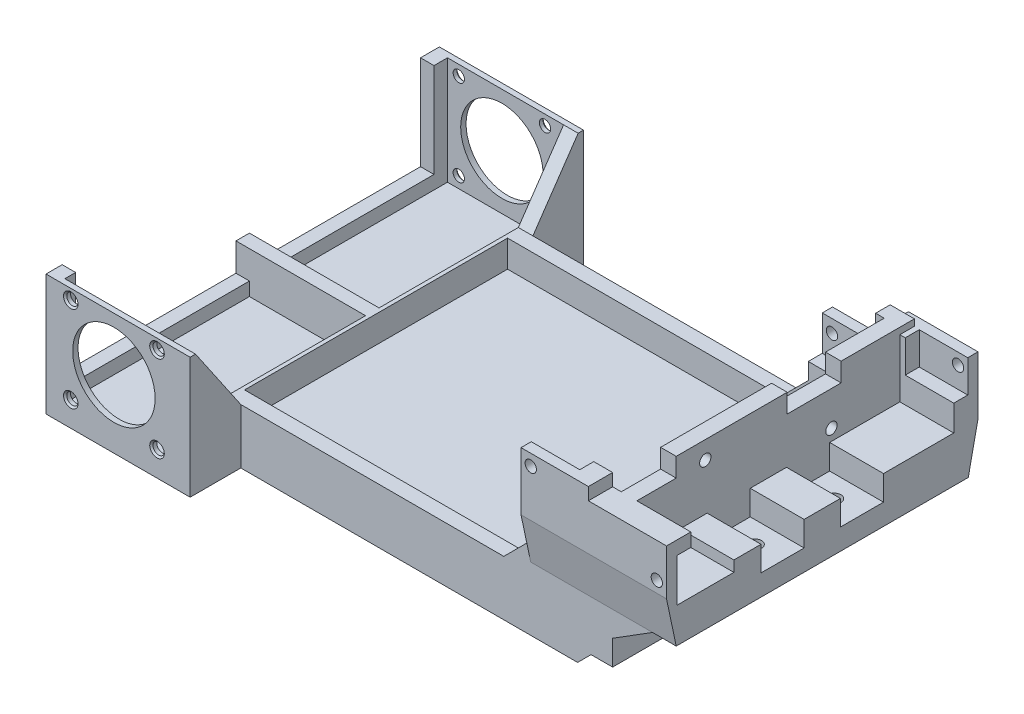
SolidWorks part; units mm, degrees
ref_plane "Front Plane" through (0, 0, 0) normal (0, 0, 1) x (1, 0, 0)
ref_plane "Top Plane" through (0, 0, 0) normal (0, 1, 0) x (1, 0, 0)
ref_plane "Right Plane" through (0, 0, 0) normal (1, 0, 0) x (0, 0, -1)
sketch "Sketch1" plane through (0, 0, 0) normal (0, 1, 0) x (1, 0, 0)
  line L0 (-12.1, 32.5) -> (-12.1, 35.5)
  line L1 (83.8983, -32.4) -> (56.8983, -32.4)
  line L2 (83.8983, -32.4) -> (83.8983, -47)
  line L3 (83.8983, -47) -> (56.8983, -47)
  line L4 (56.8983, -32.4) -> (56.8983, -47)
  line L5 (83.3, 13.5) -> (97.9, 13.5)
  line L6 (83.3, 13.5) -> (83.3, -13.5)
  line L7 (83.3, -13.5) -> (97.9, -13.5)
  line L8 (97.9, 13.5) -> (97.9, -13.5)
  line L9 (56.8983, 32.4) -> (83.8983, 32.4)
  line L10 (56.8983, 32.4) -> (56.8983, 47)
  line L11 (56.8983, 47) -> (83.8983, 47)
  line L12 (83.8983, 32.4) -> (83.8983, 47)
  line L13 (14.3, -24.25) -> (80.3, -24.25)
  line L14 (14.3, -24.25) -> (14.3, 24.25)
  line L15 (14.3, 24.25) -> (80.3, 24.25)
  line L16 (80.3, -24.25) -> (80.3, 24.25)
  line L17 (-12.1, 2.5) -> (10.1, 2.5)
  line L18 (-12.1, 2.5) -> (-12.1, 10.5)
  line L19 (-12.1, 35.5) -> (10.1, 35.5)
  line L20 (10.1, 2.5) -> (10.1, 10.5)
  line L21 (10.1, -35.5) -> (-10.1, -35.5)
  line L22 (10.1, -35.5) -> (10.1, -32.5)
  line L23 (10.1, -2.5) -> (-10.1, -2.5)
  line L24 (-10.1, -35.5) -> (-10.1, -32.5)
  line L25 (-16.1, -32.5) -> (-10.1, -32.5)
  line L26 (-16.1, -32.5) -> (-16.1, -10.5)
  line L27 (-16.1, -10.5) -> (-10.1, -10.5)
  line L28 (11.3, -32.5) -> (11.3, -10.5)
  line L29 (-16.1, 10.5) -> (-12.1, 10.5)
  line L30 (-16.1, 10.5) -> (-16.1, 32.5)
  line L31 (-16.1, 32.5) -> (-12.1, 32.5)
  line L32 (11.3, 10.5) -> (11.3, 32.5)
  line L33 (10.1, 10.5) -> (11.3, 10.5)
  line L34 (10.1, 32.5) -> (10.1, 35.5)
  line L35 (10.1, 32.5) -> (11.3, 32.5)
  line L36 (10.1, -10.5) -> (11.3, -10.5)
  line L37 (10.1, -10.5) -> (10.1, -2.5)
  line L38 (-10.1, -10.5) -> (-10.1, -2.5)
  line L39 (10.1, -32.5) -> (11.3, -32.5)
  arc A0 (86.0992, 6.7139) -> (86.0992, -6.7139) centre (89.8, 0) ccw
  arc A1 (87.0805, -8.0067) -> (92.5195, -8.0067) centre (89.8, -7.366) ccw
  arc A2 (92.5195, 8.0067) -> (87.0805, 8.0067) centre (89.8, 7.366) ccw
  arc A3 (93.5008, -6.7139) -> (93.5008, 6.7139) centre (89.8, 0) ccw
  arc A4 (92.5195, -8.0067) -> (93.5008, -6.7139) centre (94.4662, -8.4654) cw
  arc A5 (86.0992, 6.7139) -> (87.0805, 8.0067) centre (85.1338, 8.4654) ccw
  arc A6 (87.0805, -8.0067) -> (86.0992, -6.7139) centre (85.1338, -8.4654) ccw
  arc A7 (93.5008, 6.7139) -> (92.5195, 8.0067) centre (94.4662, 8.4654) cw
  point P33 (92.585, -7.1425)
  dimension "D1" = 2
  dimension "D2" = 2
  dimension "D3" = 2
  dimension "D36" = 7.6663
  dimension "D37" = 7.366
  dimension "D39" = 2.794
  dimension "D4" = 22.2
  dimension "D5" = 3
  dimension "D6" = 22
  dimension "D7" = 4
  dimension "D8" = 1.2
  dimension "D9" = 3
  dimension "D10" = 66
  dimension "D11" = 48.5
  dimension "D12" = 20.2
  dimension "D13" = 6
  dimension "D14" = 1.2
  dimension "D15" = 3
  dimension "D16" = 22
  dimension "D17" = 8
  dimension "D18" = 3
  dimension "D19" = 11.5
  dimension "D20" = 11.5
  dimension "D21" = 27
  dimension "D22" = 14.6
  dimension "D23" = 27
  dimension "D24" = 14.6
  dimension "D25" = 45.5983
  dimension "D26" = 45.5983
  dimension "D27" = 8
  dimension "D28" = 5
  dimension "D29" = 8.15
  dimension "D30" = 3
  dimension "D31" = 10.75
  dimension "D32" = 9.5
  dimension "D33" = 24.25
  dimension "D34" = 27
  dimension "D35" = 14.6
  dimension "D38" = 7.366
  dimension "D40" = 14.3
  dimension "D41" = 2.5
sketch "Sketch5" plane through (0, 0, 0) normal (0, 1, 0) x (1, 0, 0)
  line L0 (83.15, 27.1) -> (11.45, 27.1)
  line L1 (80.3, 24.25) -> (14.3, 24.25) construction
  line L2 (80.3, 24.25) -> (80.3, -24.25) construction
  line L3 (80.3, -24.25) -> (14.3, -24.25) construction
  line L4 (14.3, 24.25) -> (14.3, -24.25) construction
  line L5 (11.45, 27.1) -> (11.45, -27.1)
  line L6 (83.15, -27.1) -> (11.45, -27.1)
  line L7 (83.15, 27.1) -> (83.15, 3.8718)
  line L8 (83.15, -3.8718) -> (83.15, -27.1)
  line L9 (14.15, 24.4) -> (14.15, -24.4)
  line L10 (83.15, 27.1) -> (83.15, -27.1) construction
  line L11 (80.45, -24.4) -> (14.15, -24.4)
  line L12 (80.45, 24.4) -> (80.45, -24.4)
  line L13 (80.45, 24.4) -> (14.15, 24.4)
  arc A0 (83.15, 3.8718) -> (83.15, -3.8718) centre (89.8, 0) ccw
  dimension "D2" = 15.39
  dimension "D1" = 2.85
  dimension "D3" = 0.15
extrude "Boss-Extrude2" add sketch "Sketch5" along normal blind 5
sketch "Sketch6" plane through (0, 0, 0) normal (0, -1, 0) x (1, 0, 0)
  line L0 (83.15, -3.8718) -> (83.15, -27.1)
  line L1 (11.45, 27.1) -> (83.15, 27.1)
  line L2 (11.45, 27.1) -> (11.45, -27.1)
  line L3 (11.45, -27.1) -> (83.15, -27.1)
  line L4 (83.15, 27.1) -> (83.15, 3.8718)
  arc A0 (83.15, 3.8718) -> (83.15, -3.8718) centre (89.8, 0) ccw
  dimension "D1" = 15.39
extrude "Boss-Extrude4" add sketch "Sketch6" along normal blind 2.7
sketch "Sketch7" plane through (0, 5, 0) normal (0, 1, 0) x (1, 0, 0)
  line L1 (83.15, -27.1) -> (75.15, -27.1)
  line L2 (11.45, -27.1) -> (83.15, -27.1) construction
  line L3 (75.15, -27.1) -> (75.15, -24.4)
  line L4 (14.15, -24.4) -> (80.45, -24.4) construction
  line L5 (75.15, -24.4) -> (80.45, -24.4)
  line L6 (80.45, -24.4) -> (80.45, 24.4)
  line L7 (80.45, 24.4) -> (75.15, 24.4)
  line L8 (80.45, 24.4) -> (14.15, 24.4) construction
  line L9 (75.15, 24.4) -> (75.15, 27.1)
  line L10 (83.15, 27.1) -> (11.45, 27.1) construction
  line L11 (75.15, 27.1) -> (83.15, 27.1)
  line L14 (83.15, 27.1) -> (83.15, 3.8718)
  line L15 (83.15, -3.8718) -> (83.15, -27.1)
  arc A0 (83.15, 3.8718) -> (83.15, -3.8718) centre (89.8, 0) ccw
  dimension "D1" = 15.39
  dimension "D2" = 8
  dimension "D3" = 8
extrude "Boss-Extrude5" add sketch "Sketch7" along normal blind 1.575
sketch "Sketch8" plane through (0, 6.575, 0) normal (0, 1, 0) x (1, 0, 0)
  line L0 (75.15, -27.1) -> (83.15, -27.1) construction
  line L1 (80.45, -27.1) -> (97.95, -27.1)
  line L2 (80.45, -27.1) -> (80.45, 27.1)
  line L3 (80.45, 27.1) -> (97.95, 27.1)
  line L4 (97.95, -27.1) -> (97.95, 27.1)
  line L5 (80.45, -27.1) -> (83.15, -27.1) construction
  dimension "D1" = 54.2
  dimension "D2" = 17.5
  dimension "D3" = 2.7
extrude "Boss-Extrude6" add sketch "Sketch8" along normal blind 8.5
sketch "Sketch9" plane through (0, 0, 27.1) normal (0, 0, 1) x (1, 0, 0)
  line L0 (80.45, 15.075) -> (75.15, 6.575)
  line L1 (75.15, 6.575) -> (80.45, 6.575)
  line L2 (80.45, 6.575) -> (80.45, 15.075)
extrude "Boss-Extrude7" add sketch "Sketch9" against normal through all
sketch "Sketch10" plane through (0, 0, 0) normal (0, 1, 0) x (1, 0, 0)
  line L0 (80.45, 27.1) -> (80.45, -27.1) construction
  line L1 (14.15, 24.4) -> (80.45, 24.4)
  line L2 (14.15, 24.4) -> (14.15, -24.4)
  line L3 (14.15, -24.4) -> (80.45, -24.4)
  line L4 (80.45, 24.4) -> (80.45, -24.4)
  line L5 (14.15, -24.4) -> (80.45, -24.4) construction
extrude "Cut-Extrude1" cut sketch "Sketch10" along normal through all
sketch "Sketch11" plane through (0, 0, 27.1) normal (0, 0, 1) x (1, 0, 0)
  line L0 (90.55, 6.575) -> (83.15, 1.9375)
  line L1 (83.15, 6.575) -> (97.95, 6.575) construction
  line L2 (83.15, 6.575) -> (83.15, -2.7) construction
  line L3 (83.15, 1.9375) -> (83.15, 6.575)
  line L4 (83.15, 6.575) -> (90.55, 6.575)
extrude "Boss-Extrude8" add sketch "Sketch11" against normal blind 5
sketch "Sketch12" plane through (0, 0, -27.1) normal (0, 0, -1) x (-1, 0, 0)
  line L0 (-90.55, 6.575) -> (-83.15, 1.9375)
  line L1 (-97.95, 6.575) -> (-83.15, 6.575) construction
  line L2 (-83.15, 6.575) -> (-83.15, -2.7) construction
  line L3 (-83.15, 1.9375) -> (-83.15, 6.575)
  line L4 (-83.15, 6.575) -> (-90.55, 6.575)
extrude "Boss-Extrude9" add sketch "Sketch12" against normal blind 5
sketch "Sketch13" plane through (0, 15.075, 0) normal (0, 1, 0) x (1, 0, 0)
  line L1 (80.45, 27.1) -> (84.95, 27.1)
  line L2 (80.45, 27.1) -> (80.45, -27.1)
  line L3 (80.45, -27.1) -> (84.95, -27.1)
  line L4 (84.95, 27.1) -> (84.95, -27.1)
  dimension "D1" = 4.5
extrude "Boss-Extrude10" add sketch "Sketch13" along normal blind 12
sketch "Sketch15" plane through (0, 15.075, 0) normal (0, 1, 0) x (1, 0, 0)
  circle A0 centre (89.8, 7.366) radius 1.25
  circle A1 centre (89.8, -7.366) radius 1.25
  dimension "D1" = 2.5
  dimension "D2" = 2.5
extrude "Cut-Extrude3" cut sketch "Sketch15" against normal through all
sketch "Sketch16" plane through (0, 15.075, 0) normal (0, 1, 0) x (1, 0, 0)
  line L0 (89.8, -7.366) -> (89.8, 7.366) construction
  line L1 (89.8, -7.366) -> (84.95, -7.366) construction
  line L2 (84.95, -27.1) -> (84.95, 27.1) construction
  line L3 (84.95, -7.366) -> (84.95, -11.366) construction
  line L4 (89.8, 7.366) -> (84.95, 7.366) construction
  line L5 (84.95, -27.1) -> (84.95, 27.1) construction
  line L6 (84.95, 7.366) -> (84.95, 11.366) construction
  line L7 (97.95, -27.1) -> (97.95, 27.1) construction
  line L8 (84.95, 11.366) -> (97.95, 11.366)
  line L9 (84.95, 11.366) -> (84.95, 3.366)
  line L10 (84.95, -11.366) -> (97.95, -11.366)
  line L11 (97.95, 11.366) -> (97.95, 3.366)
  line L12 (84.95, -7.366) -> (84.95, -3.366) construction
  line L13 (84.95, -3.366) -> (97.95, -3.366)
  line L14 (84.95, 7.366) -> (84.95, 3.366) construction
  line L15 (84.95, 3.366) -> (97.95, 3.366)
  line L16 (84.95, -3.366) -> (84.95, -11.366)
  line L17 (97.95, -3.366) -> (97.95, -11.366)
  dimension "D1" = 4
  dimension "D2" = 4
  dimension "D3" = 4
  dimension "D4" = 4
extrude "Cut-Extrude4" cut sketch "Sketch16" against normal offset from surface (4.6 mm away) 3.9 up to face at (89.8, 6.575, -8.616)
sketch "Sketch17" plane through (0, 15.075, 0) normal (0, 1, 0) x (1, 0, 0)
  line L0 (84.95, -27.1) -> (97.95, -27.1) construction
  line L1 (97.95, 27.1) -> (94.95, 27.1)
  line L2 (97.95, 27.1) -> (97.95, -27.1)
  line L3 (97.95, -27.1) -> (94.95, -27.1)
  line L4 (94.95, 27.1) -> (94.95, -27.1)
  dimension "D1" = 3
extrude "Cut-Extrude5" cut sketch "Sketch17" against normal through all
sketch "Sketch18" plane through (80.45, 0, 0) normal (-1, 0, 0) x (0, 0, 1)
  line L0 (0, 27.075) -> (-13.5, 27.075) construction
  line L1 (-27.1, 27.075) -> (27.1, 27.075) construction
  line L3 (-13.5, 27.075) -> (-3.5, 27.075)
  line L4 (-13.5, 27.075) -> (-13.5, 23.575)
  line L5 (-13.5, 23.575) -> (-3.5, 23.575)
  line L6 (-3.5, 27.075) -> (-3.5, 23.575)
  dimension "D1" = 13.5
  dimension "D2" = 8.5
  dimension "D3" = 10
extrude "Cut-Extrude6" cut sketch "Sketch18" against normal through all
sketch "Sketch19" plane through (84.95, 0, 0) normal (1, 0, 0) x (0, 0, -1)
  line L0 (-27.1, 27.075) -> (27.1, 27.075) construction
  line L1 (0, 15.075) -> (0, 25.875) construction
  line L3 (-11.7, 20.475) -> (11.7, 20.475) construction
  line L4 (11.7, 20.475) -> (11.7, 17.175) construction
  line L5 (-11.7, 20.475) -> (-11.7, 23.775) construction
  line L7 (0, 27.075) -> (0, 25.875) construction
  line L8 (3.366, 15.075) -> (-3.366, 15.075) construction
  circle A0 centre (-11.7, 23.775) radius 1.05
  circle A1 centre (11.7, 17.175) radius 1.05
  point P6 (0, 0)
  point P11 (0, 20.475)
  point P15 (0, 20.475)
  dimension "D3" = 2.1
  dimension "D4" = 2.1
  dimension "D1" = 23.4
  dimension "D2" = 2.1
  dimension "D5" = 10.8
extrude "Cut-Extrude7" cut sketch "Sketch19" against normal through all
sketch "Sketch20" plane through (0, 27.075, 0) normal (0, 1, 0) x (1, 0, 0)
  line L2 (80.45, -24.4) -> (80.45, 24.4)
  line L4 (82.05, -24.4) -> (82.05, 24.4)
  line L5 (80.45, 27.1) -> (80.45, 24.4) construction
  line L6 (80.45, 24.4) -> (82.05, 24.4)
  line L7 (80.45, -27.1) -> (80.45, -24.4) construction
  line L8 (80.45, -24.4) -> (82.05, -24.4)
  dimension "D1" = 1.6
extrude "Cut-Extrude8" cut sketch "Sketch20" against normal blind 20
sketch "Sketch21" plane through (0, 0, 27.1) normal (0, 0, 1) x (1, 0, 0)
  line L0 (94.95, 15.075) -> (94.95, 17.175) construction
  line L1 (84.95, 15.075) -> (94.95, 15.075)
  line L2 (84.95, 15.075) -> (84.95, 20.075)
  line L3 (84.95, 20.075) -> (94.95, 20.075)
  line L4 (94.95, 15.075) -> (94.95, 20.075)
  line L5 (94.95, 17.175) -> (93.15, 17.175) construction
  line L6 (94.95, 6.575) -> (94.95, 15.075) construction
  circle A0 centre (93.15, 17.175) radius 1.05
  dimension "D4" = 2.1
  dimension "D1" = 5
  dimension "D2" = 2.1
  dimension "D3" = 1.8
extrude "Boss-Extrude11" add sketch "Sketch21" against normal blind 2.7 and the other way blind 1.8
sketch "Sketch23" plane through (0, 0, 27.1) normal (0, 0, 1) x (1, 0, 0)
  line L0 (67.95, 25.875) -> (67.95, 23.775) construction
  line L1 (94.95, 15.075) -> (67.95, 15.075)
  line L2 (94.95, 15.075) -> (94.95, 25.875)
  line L3 (94.95, 25.875) -> (67.95, 25.875)
  line L4 (67.95, 15.075) -> (67.95, 25.875)
  line L5 (67.95, 23.775) -> (69.75, 23.775) construction
  circle A0 centre (69.75, 23.775) radius 1.05
  circle A1 centre (93.15, 17.175) radius 1.05
  dimension "D5" = 2.1
  dimension "D6" = 2.1
  dimension "D1" = 10.8
  dimension "D2" = 27
  dimension "D3" = 2.1
  dimension "D4" = 1.8
extrude "Boss-Extrude13" add sketch "Sketch23" along normal blind 1.8 and the other way blind 2.7
sketch "Sketch22" plane through (82.05, 0, 0) normal (-1, 0, 0) x (0, 0, 1)
  line L1 (34.4916, 27.075) -> (17.1, 27.075)
  line L3 (27.9666, 23.575) -> (17.1, 23.575)
  line L4 (17.1, 27.075) -> (17.1, 23.575)
  line L5 (34.4916, 27.075) -> (34.4916, 23.575)
  line L6 (34.4916, 23.575) -> (27.9666, 23.575)
  line L7 (27.1, 27.075) -> (-3.5, 27.075) construction
  point P5 (34.4916, 25.575)
  dimension "D1" = 10
  dimension "D3" = 3.5
extrude "Cut-Extrude9" cut sketch "Sketch22" against normal through all and the other way up to surface (1.6 mm away) other way up to face at (80.45, 26.475, 25.75)
sketch "Sketch24" plane through (0, 0, 27.1) normal (0, 0, 1) x (1, 0, 0)
  line L1 (67.95, 15.075) -> (85.45, 15.075)
  line L2 (67.95, 15.075) -> (67.95, 5)
  line L3 (67.95, 5) -> (85.45, 5)
  line L4 (85.45, 15.075) -> (85.45, 5)
extrude "Boss-Extrude14" add sketch "Sketch24" against normal up to surface (2.7 mm away) up to face at (67.7577, 12.2904, 24.4)
sketch "Sketch25" plane through (0, 0, -27.1) normal (0, 0, -1) x (-1, 0, 0)
  line L0 (-94.95, 25.875) -> (-94.95, 23.775) construction
  line L1 (-94.95, 15.075) -> (-67.95, 15.075)
  line L2 (-94.95, 15.075) -> (-94.95, 25.875)
  line L3 (-94.95, 25.875) -> (-82.05, 25.875)
  line L5 (-94.95, 23.775) -> (-93.15, 23.775) construction
  line L6 (-67.95, 15.075) -> (-67.95, 17.175) construction
  line L7 (-67.95, 17.175) -> (-69.75, 17.175) construction
  line L9 (-67.95, 19.575) -> (-76.95, 19.575)
  line L10 (-76.95, 19.575) -> (-82.05, 25.875)
  line L11 (-67.95, 19.575) -> (-67.95, 15.075)
  circle A0 centre (-93.15, 23.775) radius 1.05
  circle A1 centre (-69.75, 17.175) radius 1.05
  dimension "D3" = 2.1
  dimension "D1" = 2.1
  dimension "D2" = 1.8
  dimension "D4" = 2.1
  dimension "D5" = 1.8
  dimension "D6" = 4.5
  dimension "D7" = 9
  dimension "D8" = 27
  dimension "D9" = 12.9
  dimension "D10" = 6.3
extrude "Boss-Extrude15" add sketch "Sketch25" along normal blind 1.8 and the other way blind 2.7
sketch "Sketch26" plane through (0, 0, -24.4) normal (0, 0, 1) x (1, 0, 0)
  line L0 (80.45, 15.075) -> (67.95, 15.075) construction
  line L1 (67.95, 19.575) -> (80.95, 19.575)
  line L2 (67.95, 19.575) -> (67.95, 15.075)
  line L3 (67.95, 15.075) -> (80.95, 15.075)
  line L4 (80.95, 19.575) -> (80.95, 15.075)
extrude "Cut-Extrude10" cut sketch "Sketch26" against normal blind 2.6
sketch "Sketch27" plane through (0, 0, 24.4) normal (0, 0, -1) x (-1, 0, 0)
  line L1 (-67.95, 25.875) -> (-76.95, 25.875)
  line L2 (-67.95, 25.875) -> (-67.95, 19.875)
  line L3 (-67.95, 19.875) -> (-76.95, 19.875)
  line L4 (-76.95, 25.875) -> (-76.95, 19.875)
  dimension "D1" = 6
  dimension "D2" = 9
extrude "Cut-Extrude11" cut sketch "Sketch27" against normal blind 2.6
sketch "Sketch28" plane through (0, 0, -24.4) normal (0, 0, 1) x (1, 0, 0)
  line L1 (94.95, 25.875) -> (85.95, 25.875)
  line L2 (94.95, 25.875) -> (94.95, 19.875)
  line L3 (94.95, 19.875) -> (85.95, 19.875)
  line L4 (85.95, 25.875) -> (85.95, 19.875)
  dimension "D1" = 6
  dimension "D2" = 9
extrude "Cut-Extrude12" cut sketch "Sketch28" against normal blind 2.6
sketch "Sketch29" plane through (0, 0, 24.4) normal (0, 0, -1) x (-1, 0, 0)
  line L0 (-94.95, 15.075) -> (-94.95, 13.075)
  line L2 (-94.95, 15.075) -> (-94.95, 21.075)
  line L3 (-94.95, 21.075) -> (-85.95, 21.075)
  line L5 (-94.95, 13.075) -> (-85.95, 13.075)
  line L6 (-85.95, 13.075) -> (-85.95, 21.075)
  point P5 (0, 0)
  point P8 (-90.2104, 21.075)
  dimension "D1" = 6
  dimension "D2" = 9
  dimension "D3" = 2
extrude "Cut-Extrude13" cut sketch "Sketch29" against normal blind 2.6 and the other way blind 8
sketch "Sketch30" plane through (0, 0, -27.1) normal (0, 0, -1) x (-1, 0, 0)
  line L1 (-67.95, 15.075) -> (-86.6707, 15.075)
  line L2 (-67.95, 15.075) -> (-67.95, 5)
  line L3 (-67.95, 5) -> (-86.6707, 5)
  line L4 (-86.6707, 15.075) -> (-86.6707, 5)
extrude "Boss-Extrude16" add sketch "Sketch30" against normal blind 2.7
sketch "Sketch31" plane through (0, -2.7, 0) normal (0, -1, 0) x (1, 0, 0)
  line L0 (83.15, 27.1) -> (76.65, 27.1) construction
  line L1 (83.15, 27.1) -> (11.45, 27.1) construction
  line L3 (76.65, 27.1) -> (-12.6, 27.1)
  line L4 (76.65, 27.1) -> (76.65, -27.1)
  line L5 (76.65, -27.1) -> (-12.6, -27.1)
  line L6 (-12.6, 27.1) -> (-12.6, -27.1)
  dimension "D1" = 6.5
  dimension "D2" = 24.05
extrude "Boss-Extrude17" add sketch "Sketch31" along normal blind 2.5
sketch "Sketch33" plane through (0, -5.2, 0) normal (0, -1, 0) x (1, 0, 0)
  line L0 (-12.6, 0) -> (0, 0) construction
  line L1 (-12.6, 27.1) -> (-12.6, -27.1) construction
  line L2 (-12.6, -1.25) -> (11.45, -1.25)
  line L3 (-12.6, 1.25) -> (11.45, 1.25)
  line L4 (0, 0) -> (11.45, 0) construction
  line L5 (11.45, 27.1) -> (11.45, -27.1) construction
  line L6 (-12.6, -1.25) -> (0, -1.25) construction
  line L7 (-12.6, 1.25) -> (0, 1.25) construction
  line L8 (-12.6, 1.25) -> (-12.6, -1.25)
  line L9 (11.45, 1.25) -> (11.45, -1.25)
  dimension "D1" = 1.25
  dimension "D2" = 1.25
extrude "Boss-Extrude18" add sketch "Sketch33" against normal up to surface (10.2 mm away) up to face at (40.375, 5, 0)
sketch "Sketch36" plane through (0, -5.2, 0) normal (0, -1, 0) x (1, 0, 0)
  line L1 (-12.6, 27.1) -> (11.45, 27.1)
  line L2 (-12.6, 27.1) -> (-12.6, 36.5)
  line L3 (-12.6, 36.5) -> (11.45, 36.5)
  line L4 (11.45, 27.1) -> (11.45, 36.5)
  dimension "D1" = 9.4
extrude "Boss-Extrude20" add sketch "Sketch36" against normal up to surface (2.5 mm away) up to face at (-0.575, -2.7, 14.175)
sketch "Sketch37" plane through (0, -2.7, 0) normal (0, 1, 0) x (1, 0, 0)
  line L0 (11.45, -27.1) -> (11.45, -36.5) construction
  line L1 (-12.6, -36.5) -> (11.45, -36.5)
  line L2 (-12.6, -36.5) -> (-12.6, -35.5)
  line L3 (-12.6, -35.5) -> (11.45, -35.5)
  line L4 (11.45, -36.5) -> (11.45, -35.5)
  dimension "D1" = 1
extrude "Boss-Extrude21" add sketch "Sketch37" along normal blind 20
sketch "Sketch38" plane through (0, 0, 36.5) normal (0, 0, 1) x (1, 0, 0)
  line L0 (0, 17.3) -> (8, 17.3) construction
  line L1 (-12.6, 17.3) -> (11.45, 17.3) construction
  line L2 (8, 17.3) -> (8, 15.4) construction
  line L3 (8, 15.4) -> (-8, 15.4) construction
  line L4 (8, 15.4) -> (8, -0.6) construction
  line L5 (-8, 15.4) -> (-8, -0.6) construction
  line L6 (-8, -0.6) -> (-8, 7.4) construction
  line L7 (-8, 7.4) -> (0, 7.4) construction
  circle A0 centre (8, 15.4) radius 1.05
  circle A1 centre (8, -0.6) radius 1.05
  circle A2 centre (-8, 15.4) radius 1.05
  circle A3 centre (-8, -0.6) radius 1.05
  circle A4 centre (0, 7.4) radius 7.65
  dimension "D3" = 2.1
  dimension "D8" = 15.3
  dimension "D1" = 8
  dimension "D2" = 1.9
  dimension "D4" = 16
  dimension "D5" = 16
  dimension "D6" = 16
  dimension "D7" = 8
extrude "Cut-Extrude14" cut sketch "Sketch38" against normal up to next
sketch "Sketch39" plane through (0, -2.7, 0) normal (0, 1, 0) x (1, 0, 0)
  line L0 (11.45, -27.1) -> (67.95, -27.1) construction
  line L1 (11.45, -36.5) -> (14.15, -36.5)
  line L2 (11.45, -36.5) -> (11.45, -27.1)
  line L3 (11.45, -27.1) -> (14.15, -27.1)
  line L4 (14.15, -36.5) -> (14.15, -27.1)
  dimension "D1" = 2.7
extrude "Boss-Extrude22" add sketch "Sketch39" along normal up to surface (7.7 mm away) and the other way up to surface (2.5 mm away) up to face at (26.725, 5, 0) other way up to face at (25.1667, -5.2, 12.1667)
sketch "Sketch40" plane through (0, 5, 0) normal (0, 1, 0) x (1, 0, 0)
  line L1 (14.15, -36.5) -> (11.45, -36.5)
  line L2 (14.15, -36.5) -> (14.15, -35.5)
  line L3 (14.15, -35.5) -> (11.45, -35.5)
  line L4 (11.45, -36.5) -> (11.45, -35.5)
extrude "Boss-Extrude23" add sketch "Sketch40" along normal up to surface (12.3 mm away) up to face at (-0.575, 17.3, 36)
sketch "Sketch41" plane through (14.15, 0, 0) normal (1, 0, 0) x (0, 0, -1)
  line L0 (-27.1, 5) -> (-35.5, 17.3)
  line L1 (-35.5, 17.3) -> (-35.5, 5)
  line L2 (-35.5, 5) -> (-27.1, 5)
extrude "Boss-Extrude24" add sketch "Sketch41" against normal up to surface (2.7 mm away) up to face at (11.45, 1.15, -14.175)
sketch "Sketch42" plane through (0, -2.7, 0) normal (0, 1, 0) x (1, 0, 0)
  line L1 (-12.6, -35.5) -> (-10.1, -35.5)
  line L2 (-12.6, -35.5) -> (-12.6, -33.5)
  line L3 (-12.6, -33.5) -> (-10.1, -33.5)
  line L4 (-10.1, -35.5) -> (-10.1, -33.5)
  dimension "D1" = 2.5
  dimension "D2" = 2
extrude "Boss-Extrude25" add sketch "Sketch42" along normal up to surface (20 mm away) up to face at (2.91, 17.3, 35.9)
sketch "Sketch43" plane through (0, -2.7, 0) normal (0, 1, 0) x (1, 0, 0)
  line L1 (-12.6, 27.1) -> (11.45, 27.1)
  line L2 (-12.6, 27.1) -> (-12.6, 36.5)
  line L3 (-12.6, 36.5) -> (11.45, 36.5)
  line L4 (11.45, 27.1) -> (11.45, 36.5)
  dimension "D1" = 9.4
extrude "Boss-Extrude26" add sketch "Sketch43" against normal up to surface (2.5 mm away) up to face at (26.0667, -5.2, 12.1667)
sketch "Sketch44" plane through (0, -2.7, 0) normal (0, 1, 0) x (1, 0, 0)
  line L0 (11.45, 27.1) -> (11.45, 36.5) construction
  line L1 (-12.6, 36.5) -> (11.45, 36.5)
  line L2 (-12.6, 36.5) -> (-12.6, 35.5)
  line L3 (-12.6, 35.5) -> (11.45, 35.5)
  line L4 (11.45, 36.5) -> (11.45, 35.5)
  dimension "D1" = 1
extrude "Boss-Extrude27" add sketch "Sketch44" along normal up to surface (20 mm away) up to face at (-0.8071, 17.3, 35.2143)
sketch "Sketch45" plane through (0, -2.7, 0) normal (0, 1, 0) x (1, 0, 0)
  line L0 (67.95, 27.1) -> (11.45, 27.1) construction
  line L1 (11.45, 36.5) -> (14.15, 36.5)
  line L2 (11.45, 36.5) -> (11.45, 27.1)
  line L3 (11.45, 27.1) -> (14.15, 27.1)
  line L4 (14.15, 36.5) -> (14.15, 27.1)
  dimension "D1" = 2.7
extrude "Boss-Extrude30" add sketch "Sketch45" along normal up to surface (7.7 mm away) and the other way up to surface (2.5 mm away) up to face at (25.7577, 5, 2.0846) other way up to face at (22.4125, -5.2, 0)
sketch "Sketch46" plane through (14.15, 0, 0) normal (1, 0, 0) x (0, 0, -1)
  line L0 (27.1, 5) -> (35.5, 17.3)
  line L1 (35.5, 17.3) -> (36.5, 17.3)
  line L2 (36.5, 17.3) -> (36.5, 5)
  line L3 (36.5, 5) -> (27.1, 5)
extrude "Boss-Extrude31" add sketch "Sketch46" against normal up to surface (2.7 mm away) up to face at (11.45, 11.15, -36)
sketch "Sketch47" plane through (0, -2.7, 0) normal (0, 1, 0) x (1, 0, 0)
  line L1 (-12.6, 35.5) -> (-10.1, 35.5)
  line L2 (-12.6, 35.5) -> (-12.6, 33)
  line L3 (-12.6, 33) -> (-10.1, 33)
  line L4 (-10.1, 35.5) -> (-10.1, 33)
  dimension "D1" = 2.5
  dimension "D2" = 2.5
extrude "Boss-Extrude32" add sketch "Sketch47" along normal up to surface (20 mm away) up to face at (2.91, 17.3, -35.9)
sketch "Sketch48" plane through (0, 0, -36.5) normal (0, 0, -1) x (-1, 0, 0)
  line L0 (0, 0) -> (0, 17.3) construction
  line L1 (12.6, 17.3) -> (-14.15, 17.3) construction
  line L2 (0, 17.3) -> (8, 17.3) construction
  line L3 (8, 17.3) -> (8, 15.4) construction
  line L4 (8, 15.4) -> (-8, 15.4) construction
  line L5 (-8, 15.4) -> (-8, -0.6) construction
  line L6 (8, 15.4) -> (8, -0.6) construction
  line L7 (8, 7.4) -> (0, 7.4) construction
  circle A0 centre (8, 15.4) radius 1.05
  circle A1 centre (-8, 15.4) radius 1.05
  circle A2 centre (-8, -0.6) radius 1.05
  circle A3 centre (8, -0.6) radius 1.05
  circle A4 centre (0, 7.4) radius 7.65
  dimension "D3" = 2.1
  dimension "D7" = 15.3
  dimension "D1" = 8
  dimension "D2" = 1.9
  dimension "D4" = 16
  dimension "D5" = 16
  dimension "D6" = 16
extrude "Cut-Extrude15" cut sketch "Sketch48" against normal up to surface (1 mm away) up to face at (0.675, 7.3, -35.5)
sketch "Sketch49" plane through (0, -2.7, 0) normal (0, 1, 0) x (1, 0, 0)
  line L1 (-10.1, 33) -> (-12.6, 33)
  line L2 (-10.1, 33) -> (-10.1, -33.5)
  line L3 (-10.1, -33.5) -> (-12.6, -33.5)
  line L4 (-12.6, 33) -> (-12.6, -33.5)
extrude "Boss-Extrude33" add sketch "Sketch49" along normal blind 2.5
chamfer "Chamfer1" distance 0.3 angle 45 8 edges at (-9.05, 15.4, -36.5) (6.95, -0.6, -36.5) (-9.05, -0.6, -36.5) (6.95, 15.4, -36.5) (-6.95, -0.6, 36.5) (9.05, -0.6, 36.5) (9.05, 15.4, 36.5) (-6.95, 15.4, 36.5)
chamfer "Chamfer2" distance 2.5 angle 45 1 edges at (76.65, -2.7, 0)
chamfer "Chamfer3" distance 5 angle 45 2 edges at (67.95, 5, -25.75) (67.95, 5, 25.75)
sketch "Sketch50" plane through (0, 15.075, 0) normal (0, 1, 0) x (1, 0, 0)
  line L1 (67.95, 24.4) -> (80.95, 24.4)
  line L2 (67.95, 24.4) -> (67.95, 27)
  line L3 (67.95, 27) -> (80.95, 27)
  line L4 (80.95, 24.4) -> (80.95, 27)
extrude "Cut-Extrude16" cut sketch "Sketch50" against normal blind 2
sketch "Sketch51" plane through (94.95, 0, 0) normal (1, 0, 0) x (0, 0, -1)
  line L0 (-28.9, 15.075) -> (-27.1, 6.575)
  line L1 (-27.1, 6.575) -> (-27.1, 15.075)
  line L2 (-27.1, 15.075) -> (-28.9, 15.075)
extrude "Boss-Extrude34" add sketch "Sketch51" against normal up to surface (27 mm away) up to face at (67.95, 17.7063, 26.85)
sketch "Sketch52" plane through (94.95, 0, 0) normal (1, 0, 0) x (0, 0, -1)
  line L0 (28.9, 15.075) -> (27.1, 6.575)
  line L1 (27.1, 6.575) -> (27.1, 15.075)
  line L2 (27.1, 15.075) -> (28.9, 15.075)
extrude "Boss-Extrude35" add sketch "Sketch52" against normal up to surface (27 mm away) up to face at (67.95, 14.4312, -26.85)
sketch "Sketch53" plane through (0, 5, 0) normal (0, 1, 0) x (1, 0, 0)
  line L0 (14.15, -24.4) -> (80.45, -24.4) construction
  line L1 (14.15, 24.4) -> (12.15, 24.4)
  line L2 (14.15, 24.4) -> (14.15, -24.4)
  line L3 (14.15, -24.4) -> (12.15, -24.4)
  line L4 (12.15, 24.4) -> (12.15, -24.4)
  dimension "D1" = 2
extrude "Cut-Extrude17" cut sketch "Sketch53" against normal up to surface (5 mm away) up to face at (47.3, 0, 0)
